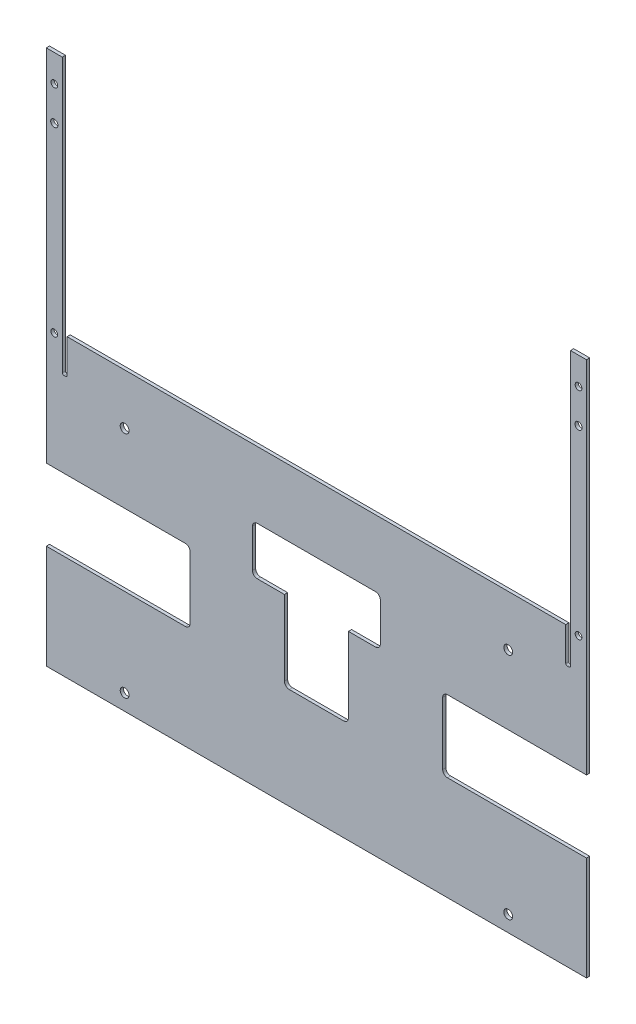
SolidWorks part; units mm, degrees
ref_plane "Plan de face" through (0, 0, 0) normal (0, 0, 1) x (1, 0, 0)
ref_plane "Plan de dessus" through (0, 0, 0) normal (0, 1, 0) x (1, 0, 0)
ref_plane "Plan de droite" through (0, 0, 0) normal (1, 0, 0) x (0, 0, -1)
sketch "Esquisse1" plane through (0, 0, 0) normal (0, 0, 1) x (1, 0, 0)
  line L1 (-169, -167.5) -> (169, -167.5)
  line L2 (-169, -167.5) -> (-169, 167.5)
  line L3 (-169, 167.5) -> (169, 167.5)
  line L4 (169, -167.5) -> (169, 167.5)
  line L5 (-169, -167.5) -> (169, 167.5) construction
  line L6 (-169, 167.5) -> (169, -167.5) construction
  point P0 (0, 0)
  dimension "D1" = 338
  dimension "D2" = 335
extrude "Boss.-Extru.1" add sketch "Esquisse1" along normal blind 2
sketch "Esquisse2" plane through (0, 0, 2) normal (0, 0, 1) x (1, 0, 0)
  line L0 (0, 0) -> (0, 137.1014) construction
  line L1 (169, 167.5) -> (-169, 167.5) construction
  line L2 (-159, 167.5) -> (159, 167.5)
  line L4 (-159, 17.5) -> (159, 17.5)
  line L5 (159, 167.5) -> (159, 17.5)
  line L6 (169, -167.5) -> (169, 167.5) construction
  line L7 (169, -102.5) -> (79, -102.5)
  line L8 (169, -102.5) -> (169, -57.5)
  line L9 (169, -57.5) -> (79, -57.5)
  line L10 (79, -102.5) -> (79, -57.5)
  line L12 (-79, -102.5) -> (-79, -57.5)
  line L13 (-169, -57.5) -> (-79, -57.5)
  line L14 (-169, -102.5) -> (-169, -57.5)
  line L15 (-169, -102.5) -> (-79, -102.5)
  line L16 (-159, 167.5) -> (-159, 17.5)
  point P6 (0, 167.5)
  point P23 (0, 17.5)
  dimension "D1" = 10
  dimension "D2" = 150
  dimension "D3" = 45
  dimension "D4" = 90
  dimension "D5" = 57.5
extrude "Enlèv. mat.-Extru.1" cut sketch "Esquisse2" against normal through all
sketch "Esquisse7" plane through (0, 0, 2) normal (0, 0, 1) x (1, 0, 0)
  line L0 (-215.3551, -157.5) -> (250.1125, -157.5) construction
  line L1 (-236.7172, -14.17) -> (327.7633, -14.17) construction
  line L2 (-169, -167.5) -> (169, -167.5) construction
  line L3 (0, 0) -> (0, -264.1515) construction
  line L4 (-120, -14.17) -> (-120, -157.5) construction
  line L5 (120, -14.17) -> (120, -157.5) construction
  circle A0 centre (-120, -157.5) radius 2.75
  circle A1 centre (-120, -14.17) radius 2.75
  circle A2 centre (120, -14.17) radius 2.75
  circle A3 centre (120, -157.5) radius 2.75
  dimension "D3" = 5.5
  dimension "D1" = 10
  dimension "D2" = 143.33
  dimension "D4" = 120
extrude "Enlèv. mat.-Extru.4" cut sketch "Esquisse7" against normal through all
hole_wizard "Dégagement M41" positions "Esquisse4" profile "Esquisse3" hole size "M4" standard "Ansi Metric" end condition through all
sketch "Esquisse4" plane through (0, 0, 2) normal (0, 0, 1) x (1, 0, 0)
  line L0 (164, 129.17) -> (164, 167.5)
  line L1 (169, 167.5) -> (159, 167.5) construction
  line L3 (-164, 129.17) -> (-164, 167.5)
  line L4 (-159, 167.5) -> (-169, 167.5) construction
  circle A0 centre (120, -14.17) radius 2.75 construction
  point P0 (164, 129.17)
  point P2 (-164, 129.17)
  dimension "D1" = 143.34
sketch "Esquisse3" plane through (164, 129.17, 2) normal (1, 0, 0) x (0, -1, 0)
  line L0 (0, 0) -> (0, 2)
  line L1 (0, 2) -> (2.25, 2)
  line L2 (2.25, 2) -> (2.25, 0)
  line L5 (2.25, 0) -> (0, 0)
  line L11 (0, -6.35) -> (0, 107.95) construction
  dimension "Diamètre du perçage jusqu'au prochain" = 4.5
  dimension "Profondeur du perçage jusqu'au prochain" = 2
sketch "Esquisse5" plane through (0, 0, 2) normal (0, 0, 1) x (1, 0, 0)
  line L0 (0, 0) -> (0, -179.3466) construction
  line L1 (156, 17.5) -> (156, -4.5)
  line L2 (-159, 17.5) -> (-156, 17.5)
  line L3 (-159, 17.5) -> (-159, -4.5)
  line L4 (-159, -4.5) -> (-156, -4.5)
  line L5 (-156, 17.5) -> (-156, -4.5)
  line L6 (159, -4.5) -> (156, -4.5)
  line L7 (159, 17.5) -> (159, -4.5)
  line L8 (159, 17.5) -> (156, 17.5)
  dimension "D1" = 22
  dimension "D2" = 3
extrude "Enlèv. mat.-Extru.2" cut sketch "Esquisse5" against normal through all
sketch "Esquisse6" plane through (0, 0, 2) normal (0, 0, 1) x (1, 0, 0)
  line L0 (0, 0) -> (0, -207.4805) construction
  line L1 (-164, 129.7438) -> (-164, 97.138) construction
  line L2 (-169, 141.2413) -> (-159, 141.2413) construction
  line L3 (-159, 167.5) -> (-159, -4.5) construction
  line L4 (-169, 167.5) -> (-169, -57.5) construction
  circle A0 centre (-164, 15.5) radius 2.1
  circle A1 centre (-164, 150.5) radius 2.1
  circle A2 centre (-120, -14.17) radius 2.75 construction
  circle A3 centre (164, 15.5) radius 2.1
  circle A4 centre (164, 150.5) radius 2.1
  point P9 (-164, 141.2413)
  dimension "D1" = 4.2
  dimension "D3" = 29.67
  dimension "D2" = 135
extrude "Enlèv. mat.-Extru.3" cut sketch "Esquisse6" against normal through all
sketch "Esquisse8" plane through (0, 0, 2) normal (0, 0, 1) x (1, 0, 0)
  line L0 (0, 0) -> (0, -208.397) construction
  line L1 (0, 0) -> (249.5077, 0) construction
  line L2 (20, -54.17) -> (40, -54.17)
  line L3 (-40, -24.17) -> (40, -24.17)
  line L4 (-40, -24.17) -> (-40, -54.17)
  line L5 (-40, -54.17) -> (-20, -54.17)
  line L6 (40, -24.17) -> (40, -54.17)
  line L7 (-40, -24.17) -> (40, -54.17) construction
  line L8 (-40, -54.17) -> (40, -24.17) construction
  line L9 (-20, -104.17) -> (20, -104.17)
  line L10 (-20, -104.17) -> (-20, -54.17)
  line L12 (20, -104.17) -> (20, -54.17)
  line L13 (-20, -104.17) -> (20, -54.17) construction
  line L14 (-20, -54.17) -> (20, -104.17) construction
  circle A0 centre (120, -14.17) radius 2.75 construction
  point P1 (0, -39.17)
  point P13 (0, -79.17)
  dimension "D1" = 10
  dimension "D2" = 30
  dimension "D3" = 80
  dimension "D4" = 50
  dimension "D5" = 40
extrude "Enlèv. mat.-Extru.5" cut sketch "Esquisse8" against normal blind 10
fillet "Congé1" radius 1 4 edges at (156, -4.5, 1) (159, -4.5, 1) (-156, -4.5, 1) (-159, -4.5, 1)
fillet "Congé2" radius 3 10 edges at (79, -57.5, 1) (79, -102.5, 1) (-40, -54.17, 1) (-20, -104.17, 1) (20, -104.17, 1) (40, -54.17, 1) (40, -24.17, 1) (-40, -24.17, 1) (-79, -102.5, 1) (-79, -57.5, 1)
equation "\"rayon_pignon\" = 26.0313"
equation "\"largeur_robot\" = 436mm"
equation "\"largeur_chenille\"= \"RD1@Annotations\""
equation "\"espace_sous_robot\"= \"largeur_robot\" - \"largeur_chenille\" - \"largeur_chenille\""
